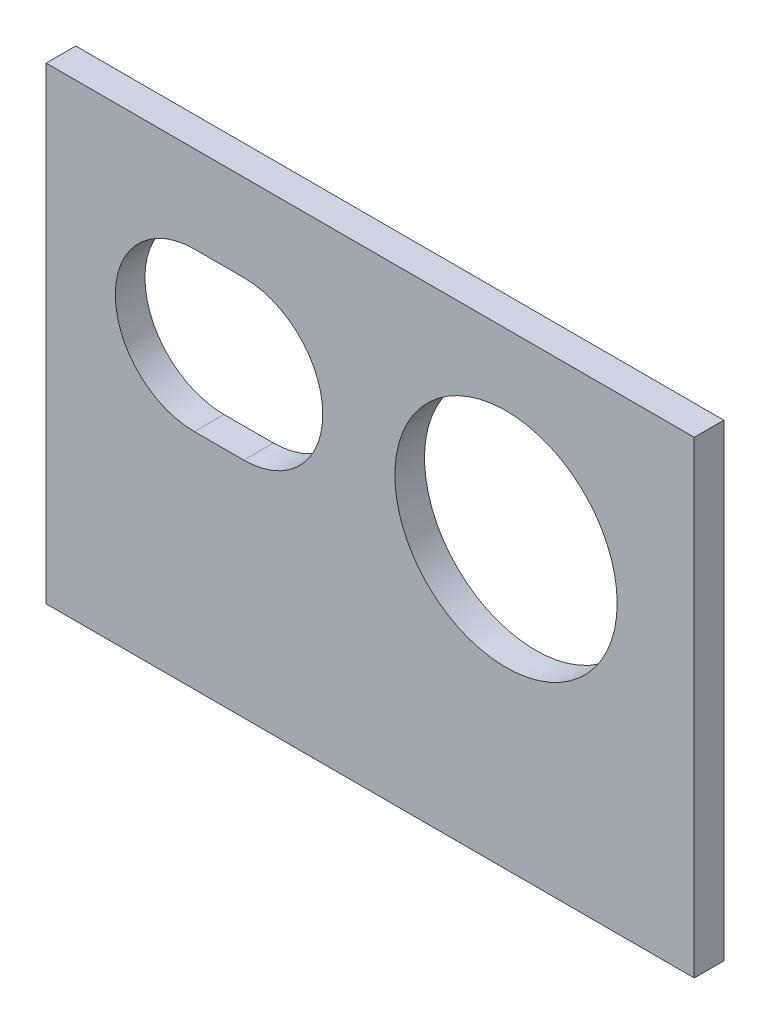
SolidWorks part; units mm, degrees
ref_plane "Front Plane" through (0, 0, 0) normal (0, 0, 1) x (1, 0, 0)
ref_plane "Top Plane" through (0, 0, 0) normal (0, 1, 0) x (1, 0, 0)
ref_plane "Right Plane" through (0, 0, 0) normal (1, 0, 0) x (0, 0, -1)
sketch "Sketch1" plane through (0, 0, 0) normal (0, 0, 1) x (1, 0, 0)
  line L1 (0, 0) -> (65.6, 0)
  line L2 (0, 0) -> (0, -47.4)
  line L3 (0, -47.4) -> (65.6, -47.4)
  line L4 (65.6, 0) -> (65.6, -47.4)
  dimension "D1" = 47.4
  dimension "D2" = 65.6
extrude "Boss-Extrude1" add sketch "Sketch1" along normal blind 3
sketch "Sketch2" plane through (0, 0, 3) normal (0, 0, 1) x (1, 0, 0)
  line L0 (65.6, -47.4) -> (65.6, 0) construction
  line L1 (65.6, 0) -> (0, 0) construction
  line L2 (15, -16.8) -> (20, -16.8) construction
  line L3 (15, -8.8) -> (20, -8.8)
  line L4 (15, -24.8) -> (20, -24.8)
  line L5 (0, 0) -> (0, -47.4) construction
  circle A0 centre (46.55, -18.45) radius 11.25
  arc A1 (15, -8.8) -> (15, -24.8) centre (15, -16.8) ccw
  arc A2 (20, -24.8) -> (20, -8.8) centre (20, -16.8) ccw
  point P8 (17.5, -16.8)
  point P13 (28, -16.8)
  point P14 (7, -16.8)
  dimension "D1" = 22.5
  dimension "D2" = 19.05
  dimension "D3" = 18.45
  dimension "D4" = 16
  dimension "D5" = 21
  dimension "D6" = 28
  dimension "D7" = 16.8
extrude "Cut-Extrude1" cut sketch "Sketch2" against normal up to next
